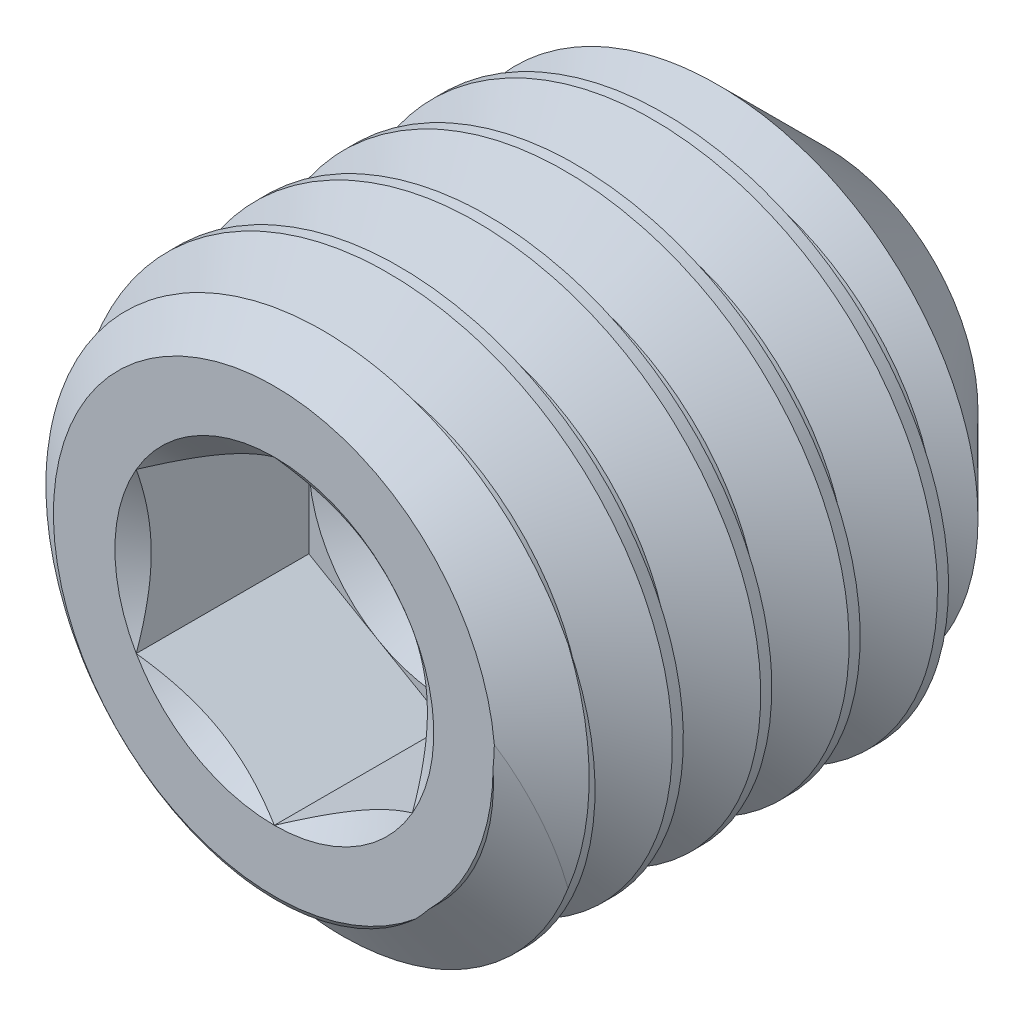
SolidWorks part; units mm, degrees
ref_plane "Front" through (0, 0, 0) normal (0, 0, 1) x (1, 0, 0)
ref_plane "Top" through (0, 0, 0) normal (0, 1, 0) x (1, 0, 0)
ref_plane "Right" through (0, 0, 0) normal (1, 0, 0) x (0, 0, -1)
sketch "Body Sketch" plane through (0, 0, 0) normal (1, 0, 0) x (0, 0, -1)
  line L0 (-2.0884, 0) -> (-2.0884, 2)
  line L1 (-2.0884, 2) -> (-1.7383, 2.5)
  line L2 (-1.7383, 2.5) -> (1.7815, 2.5)
  line L3 (1.7815, 2.5) -> (2.9116, 1.3699)
  line L4 (0.0216, 2.5) -> (0.0216, -2.5) construction
  line L5 (2.0884, 0) -> (-2.0884, 0)
  line L6 (-2.0884, 2) -> (-2.0884, -2) construction
  line L7 (2.0884, 0) -> (2.9116, 1.3699)
  line L8 (2.0884, 0) -> (2.9116, -1.3699) construction
  line L10 (2.0884, 0) -> (2.9116, 0) construction
  line L11 (2.9116, 1.3699) -> (2.9116, 0) construction
  point P11 (0.0216, 0)
  dimension "Length" = 5
  dimension "Top Chamfer" = 35
  dimension "Diameter" = 5
  dimension "D1" = 4
  dimension "D2" = 118
  dimension "D3" = 45
revolve "Body Revolve" add sketch "Body Sketch" angle 360 about L5
ref_plane "Bottom of Tip Plane" through (0, 0, -2.9116) normal (0, 0, 1) x (1, 0, 0)
sketch "Spiral Sketch" plane through (0, 0, -2.9116) normal (0, 0, 1) x (1, 0, 0)
  circle A0 centre (0, 0) radius 2.5 construction
  circle A1 centre (0, 0) radius 2.5
curve "Helix/Spiral" pitch 0.8 height 5.8 radius 2.5 centre (0, 0, -2.9116) axis (0, 0, 1) start towards (0, 1, 0) parameters "Thread Pitch"=0.8
sketch "Cut Sweep Sketch" plane through (0, 0, 0) normal (1, 0, 0) x (0, 0, -1)
  line L0 (2.9116, 2.5) -> (3.6116, 2.5)
  line L1 (3.6116, 2.5) -> (3.3116, 1.9804)
  line L2 (3.3116, 1.9804) -> (3.2116, 1.9804)
  line L3 (3.2116, 1.9804) -> (2.9116, 2.5)
  line L4 (3.0616, 2.2402) -> (3.4616, 2.2402) construction
  line L6 (-1.7383, 2.5) -> (1.7815, 2.5) construction
  dimension "D1" = 0.1
  dimension "D3" = 60
  dimension "D2" = 0.4
sweep "Cut Sweep" cut profiles "Cut Sweep Sketch" path "Helix/Spiral" align with end faces yes
sketch "Hex Sketch" plane through (0, 0, 2.0884) normal (0, 0, 1) x (1, 0, 0)
  line L1 (0, 1.4434) -> (-1.25, 0.7217)
  line L2 (-1.25, 0.7217) -> (-1.25, -0.7217)
  line L3 (-1.25, -0.7217) -> (0, -1.4434)
  line L4 (0, -1.4434) -> (1.25, -0.7217)
  line L5 (1.25, -0.7217) -> (1.25, 0.7217)
  line L6 (1.25, 0.7217) -> (0, 1.4434)
  circle A0 centre (0, 0) radius 1.25 construction
  dimension "Hex" = 2.5
extrude "Hex Extrude" cut sketch "Hex Sketch" against normal blind 1.5625
sketch "Hex Entry Sketch" plane through (0, 0, 2.0884) normal (0, 0, 1) x (1, 0, 0)
  circle A0 centre (0, 0) radius 1.4434
extrude "Hex Entry Extrude" cut sketch "Hex Entry Sketch" against normal through all draft 55
sketch "Hex Bottom Sketch" plane through (0, 0, 0.5259) normal (0, 0, 1) x (1, 0, 0)
  circle A0 centre (0, 0) radius 1.25 construction
  circle A1 centre (0, 0) radius 1.25
extrude "Hex Bottom Extrude" cut sketch "Hex Bottom Sketch" against normal through all draft 60
equation "\"D1@Cut Sweep Sketch\" = \"Thread Pitch@Helix/Spiral\" * .125"
equation "\"D2@Cut Sweep Sketch\" = \"Thread Pitch@Helix/Spiral\" * .5"
equation "\"D3@Helix/Spiral\" = \"Length@Body Sketch\" + \"Thread Pitch@Helix/Spiral\""
equation "\"hex Depth@Hex Extrude\" = \"Hex@Hex Sketch\" * .625"
equation "\"D1@Body Sketch\" = \"Diameter@Body Sketch\" * .8"
equation "\"Diameter\"= 5mm"
equation "\"Thread Pitch\"= 0.8mm"
equation "\"Hex Size\"= 2.5mm"
equation "\"Diameter@Body Sketch\"=\"Diameter\""
equation "\"Thread Pitch@Helix/Spiral\"=\"Thread Pitch\""
equation "\"Hex@Hex Sketch\"=\"Hex Size\""
